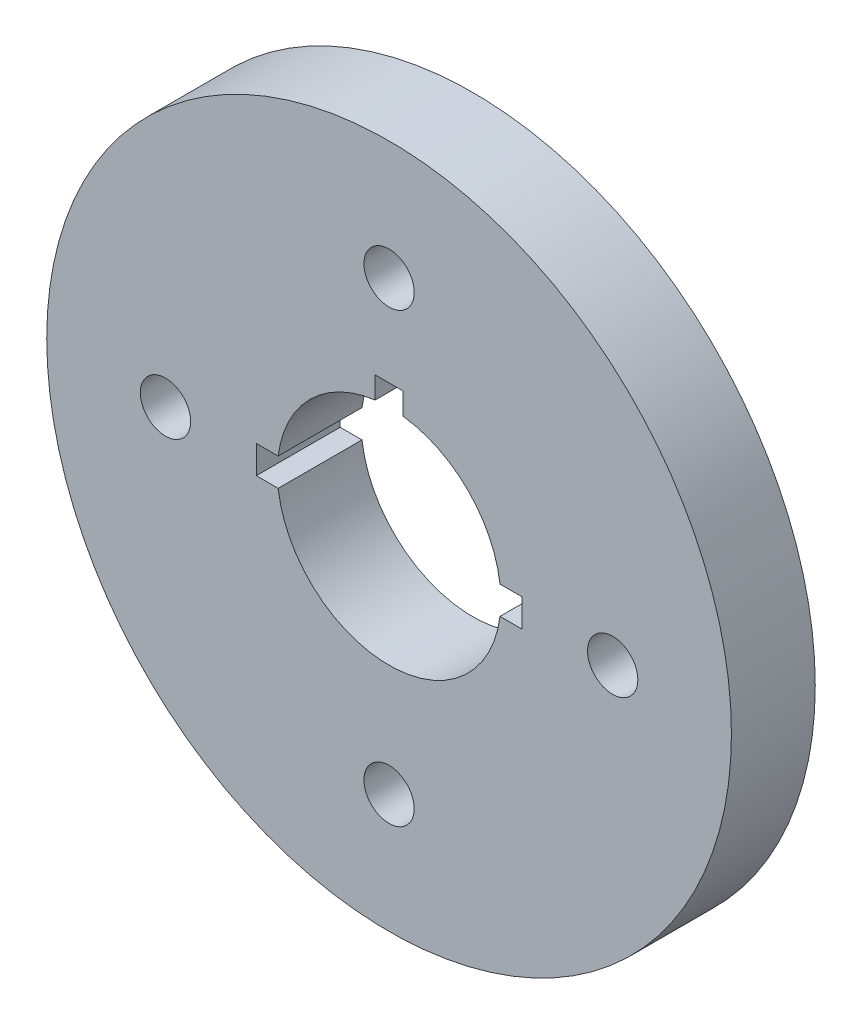
SolidWorks part; units mm, degrees
ref_plane "Front Plane" through (0, 0, 0) normal (0, 0, 1) x (1, 0, 0)
ref_plane "Top Plane" through (0, 0, 0) normal (0, 1, 0) x (1, 0, 0)
ref_plane "Right Plane" through (0, 0, 0) normal (1, 0, 0) x (0, 0, -1)
sketch "Sketch1" plane through (0, 0, 0) normal (0, 0, 1) x (1, 0, 0)
  line L2 (-0.2262, -3.9936) -> (-0.6928, -12.2304)
  line L3 (-2.4019, -3.1985) -> (-7.356, -9.7955)
  arc A2 (-0.2262, -3.9936) -> (-2.4019, -3.1985) centre (0, 0) ccw
  arc A3 (-0.6928, -12.2304) -> (-7.356, -9.7955) centre (0, 0) ccw
  circle A4 centre (0, 0) radius 4
  circle A5 centre (0, 0) radius 12.25
extrude "Boss-Extrude1" add sketch "Sketch1" along normal blind 3 contours L3 A5 L2 A4 | L2 A3 L3 A2
sketch "Sketch2" plane through (0, 0, 3) normal (0, 0, 1) x (1, 0, 0)
  line L1 (-4.75, 0.5) -> (4.75, 0.5)
  line L2 (-4.75, 0.5) -> (-4.75, -0.5)
  line L3 (-4.75, -0.5) -> (4.75, -0.5)
  line L4 (4.75, 0.5) -> (4.75, -0.5)
  line L5 (-4.75, 0.5) -> (4.75, -0.5) construction
  line L6 (-4.75, -0.5) -> (4.75, 0.5) construction
  line L8 (-0.5, -0.5) -> (-0.5, 4.75)
  line L9 (-0.5, 4.75) -> (0.5, 4.75)
  line L10 (0.5, -0.5) -> (0.5, 4.75)
  line L11 (-0.0526, -0.5) -> (0.5, 4.75) construction
  line L12 (-0.5, 4.75) -> (0.0526, -0.5) construction
  point P0 (0, 0)
  point P6 (0, 0)
  circle M6 centre (0, 0) radius 4
  dimension "D1" = 1
  dimension "D2" = 9.5
  dimension "D3" = 1
  dimension "D4" = 5.25
extrude "Cut-Extrude1" cut sketch "Sketch2" against normal blind 3 contours L10 L9 L8 M6 | L2 L3 L1 M6 | L4 L1 L3 M6 region at (-4.3697, 0, 3) region at (0, 4.3697, 3) region at (4.3697, 0, 3)
sketch "Sketch5" plane through (0, 0, 3) normal (0, 0, 1) x (1, 0, 0)
  line L0 (0, 0) -> (0, -8) construction
  circle A0 centre (0, -8) radius 0.9
  circle A1 centre (-8, 0) radius 0.9
  circle A2 centre (0, 8) radius 0.9
  circle A3 centre (8, 0) radius 0.9
  point P13 (0, 0)
  dimension "D2" = 4
  dimension "D1" = 8
extrude "Cut-Extrude2" cut sketch "Sketch5" against normal blind 3
